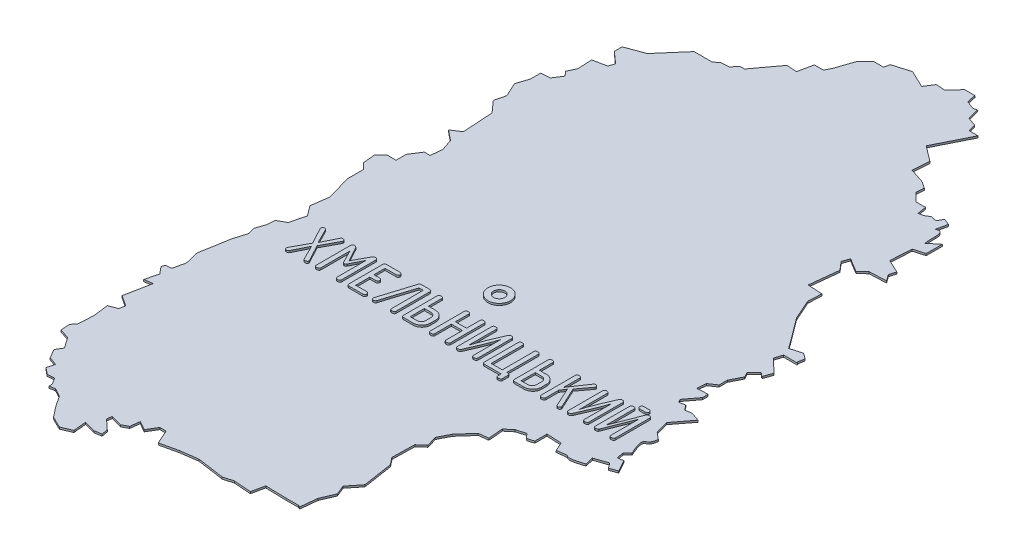
SolidWorks part; units mm, degrees
ref_plane "Спереди" through (0, 0, 0) normal (0, 0, 1) x (1, 0, 0)
ref_plane "Сверху" through (0, 0, 0) normal (0, 1, 0) x (1, 0, 0)
ref_plane "Справа" through (0, 0, 0) normal (1, 0, 0) x (0, 0, -1)
sketch "Эскиз1" plane through (0, 0, 0) normal (0, 1, 0) x (1, 0, 0)
  line B0 (-2553.4518, 8644.0645) -> (-2569.022, 8642.1265)
  line B1 (-2569.022, 8642.1265) -> (-2572.2555, 8660.9301)
  line B2 (-2572.2555, 8660.9301) -> (-2560.5867, 8673.2542)
  line B3 (-2556.6903, 8739.4542) -> (-2575.4889, 8755.0244)
  line B4 (-2575.4889, 8755.0244) -> (-2584.5897, 8789.4185)
  line B5 (-2584.5897, 8789.4185) -> (-2548.2499, 8836.7819)
  line B6 (-2548.2499, 8836.7819) -> (-2572.2555, 8845.2249)
  line B7 (-2572.2555, 8845.2249) -> (-2589.1363, 8841.9889)
  line B8 (-2589.1363, 8841.9889) -> (-2599.5147, 8855.6262)
  line B9 (-2599.5147, 8855.6262) -> (-2615.0773, 8852.3648)
  line B10 (-2615.0773, 8852.3648) -> (-2620.2843, 8860.8103)
  line B11 (-2620.2843, 8860.8103) -> (-2594.3306, 8895.1765)
  line B12 (-2594.3306, 8895.1765) -> (-2594.3306, 8910.132)
  line B13 (-2594.3306, 8910.132) -> (-2623.5203, 8908.8316)
  line B14 (-2623.5203, 8908.8316) -> (-2621.5823, 8932.8498)
  line B15 (-2621.5823, 8932.8498) -> (-2601.4655, 8946.4693)
  line B16 (-2601.4655, 8946.4693) -> (-2601.4655, 8968.5216)
  line B17 (-2601.4655, 8968.5216) -> (-2585.8953, 8999.0168)
  line B18 (-2585.8953, 8999.0168) -> (-2593.0352, 9012.6541)
  line B19 (-2593.0352, 9012.6541) -> (-2574.2214, 9031.4755)
  line B20 (-2574.2214, 9031.4755) -> (-2563.8176, 9023.0274)
  line B21 (-2563.8176, 9023.0274) -> (-2555.3848, 9047.0355)
  line B22 (-2555.3848, 9047.0355) -> (-2591.0692, 9080.787)
  line B23 (-2591.0692, 9080.787) -> (-2584.5897, 9101.5591)
  line B24 (-2584.5897, 9101.5591) -> (-2546.9444, 9101.5591)
  line B25 (-2546.9444, 9101.5591) -> (-2550.2133, 9103.5099)
  line B26 (-2550.2133, 9103.5099) -> (-2546.9444, 9121.6683)
  line B27 (-2546.9444, 9121.6683) -> (-2563.1851, 9133.3574)
  line B28 (-2563.1851, 9133.3574) -> (-2563.8176, 9132.0645)
  line B29 (-2563.8176, 9132.0645) -> (-2593.0352, 9123.6292)
  line B30 (-2593.0352, 9123.6292) -> (-2607.9577, 9144.3835)
  line B31 (-2607.9577, 9144.3835) -> (-2652.7176, 9204.0939)
  line B32 (-2652.7176, 9204.0939) -> (-2676.7384, 9258.5921)
  line B33 (-2676.7384, 9258.5921) -> (-2674.7826, 9294.2816)
  line B34 (-2674.7826, 9294.2816) -> (-2713.7258, 9296.2374)
  line B35 (-2713.7258, 9296.2374) -> (-2705.2905, 9372.8032)
  line B36 (-2705.2905, 9372.8032) -> (-2724.1144, 9394.8809)
  line B37 (-2724.1144, 9394.8809) -> (-2717.6298, 9413.6921)
  line B38 (-2717.6298, 9413.6921) -> (-2681.2799, 9391.6271)
  line B39 (-2681.2799, 9391.6271) -> (-2663.1138, 9408.5029)
  line B40 (-2663.1138, 9408.5029) -> (-2618.3412, 9410.4435)
  line B41 (-2618.3412, 9410.4435) -> (-2630.678, 9427.3243)
  line B42 (-2630.678, 9427.3243) -> (-2625.4888, 9444.8427)
  line B43 (-2625.4888, 9444.8427) -> (-2661.1707, 9461.7057)
  line B44 (-2661.1707, 9461.7057) -> (-2657.9195, 9518.1801)
  line B45 (-2657.9195, 9518.1801) -> (-2628.7273, 9526.6154)
  line B46 (-2628.7273, 9526.6154) -> (-2628.7273, 9569.4449)
  line B47 (-2628.7273, 9569.4449) -> (-2654.0308, 9548.6804)
  line B48 (-2672.8522, 9594.7535) -> (-2666.3548, 9623.9482)
  line B49 (-2666.3548, 9623.9482) -> (-2683.223, 9630.443)
  line B50 (-2683.223, 9630.443) -> (-2691.6659, 9615.518)
  line B51 (-2691.6659, 9615.518) -> (-2707.2234, 9618.759)
  line B52 (-2707.2234, 9618.759) -> (-2718.9379, 9611.6115)
  line B53 (-2718.9379, 9611.6115) -> (-2732.5625, 9608.3653)
  line B54 (-2732.5625, 9608.3653) -> (-2736.4411, 9632.3861)
  line B55 (-2736.4411, 9632.3861) -> (-2761.7445, 9632.3861)
  line B56 (-2761.7445, 9632.3861) -> (-2783.8146, 9654.4587)
  line B57 (-2783.8146, 9654.4587) -> (-2782.5141, 9675.2105)
  line B58 (-2782.5141, 9675.2105) -> (-2799.3772, 9686.8971)
  line B59 (-2799.3772, 9686.8971) -> (-2840.2763, 9700.5242)
  line B60 (-2840.2763, 9700.5242) -> (-2837.0301, 9744.6541)
  line B61 (-2837.0301, 9744.6541) -> (-2877.9089, 9775.7894)
  line B62 (-2877.9089, 9775.7894) -> (-2831.8308, 9867.9533)
  line B63 (-2831.8308, 9867.9533) -> (-2855.8388, 9867.9533)
  line B64 (-2855.8388, 9867.9533) -> (-2861.0509, 9888.0701)
  line B65 (-2861.0509, 9888.0701) -> (-2884.3935, 9896.5055)
  line B66 (-2884.3935, 9896.5055) -> (-2892.8365, 9927.0007)
  line B67 (-2892.8365, 9927.0007) -> (-2901.9246, 9924.4175)
  line B68 (-2901.9246, 9924.4175) -> (-2923.9845, 9932.8554)
  line B69 (-2923.9845, 9932.8554) -> (-2929.1864, 9956.8559)
  line B70 (-2929.1864, 9956.8559) -> (-2956.4228, 9956.8559)
  line B71 (-2956.4228, 9956.8559) -> (-2981.7339, 9928.9438)
  line B72 (-2981.7339, 9928.9438) -> (-3005.742, 9930.8971)
  line B73 (-3005.742, 9930.8971) -> (-3021.3173, 9906.8839)
  line B74 (-3021.3173, 9906.8839) -> (-3067.4158, 9928.9438)
  line B75 (-3067.4158, 9928.9438) -> (-3113.4583, 9915.3243)
  line B76 (-3113.4583, 9915.3243) -> (-3116.707, 9900.4095)
  line B77 (-3116.707, 9900.4095) -> (-3142.6683, 9900.4095)
  line B78 (-3142.6683, 9900.4095) -> (-3166.0287, 9876.3887)
  line B79 (-3166.0287, 9876.3887) -> (-3181.6167, 9830.3182)
  line B80 (-3181.6167, 9830.3182) -> (-3190.0546, 9813.45)
  line B81 (-3190.0546, 9813.45) -> (-3214.0601, 9813.45)
  line B82 (-3214.0601, 9813.45) -> (-3222.5056, 9773.8413)
  line B83 (-3222.5056, 9773.8413) -> (-3249.7395, 9775.7894)
  line B84 (-3249.7395, 9775.7894) -> (-3297.7582, 9710.9128)
  line B85 (-3297.7582, 9710.9128) -> (-3309.4625, 9710.9128)
  line B86 (-3309.4625, 9710.9128) -> (-3323.0744, 9695.3349)
  line B87 (-3323.0744, 9695.3349) -> (-3343.8363, 9694.0497)
  line B88 (-3343.8363, 9694.0497) -> (-3357.4787, 9683.6484)
  line B89 (-3357.4787, 9683.6484) -> (-3405.5101, 9683.6484)
  line B90 (-3405.5101, 9683.6484) -> (-3463.2417, 9616.8134)
  line B91 (-3463.2417, 9616.8134) -> (-3512.5762, 9598.6295)
  line B92 (-3512.5762, 9598.6295) -> (-3512.5762, 9577.8828)
  line B93 (-3512.5762, 9577.8828) -> (-3482.0758, 9550.6286)
  line B94 (-3482.0758, 9550.6286) -> (-3487.2574, 9535.0508)
  line B95 (-3487.2574, 9535.0508) -> (-3512.5762, 9529.8514)
  line B96 (-3512.5762, 9529.8514) -> (-3522.947, 9527.921)
  line B97 (-3522.947, 9527.921) -> (-3521.009, 9488.9777)
  line B98 (-3521.009, 9488.9777) -> (-3531.3976, 9466.928)
  line B99 (-3531.3976, 9466.928) -> (-3521.009, 9454.5836)
  line B100 (-3521.009, 9454.5836) -> (-3536.5868, 9430.5755)
  line B101 (-3536.5868, 9430.5755) -> (-3560.5822, 9429.2623)
  line B102 (-3560.5822, 9429.2623) -> (-3560.5822, 9402.0259)
  line B103 (-3560.5822, 9402.0259) -> (-3570.9682, 9369.5698)
  line B104 (-3570.9682, 9369.5698) -> (-3553.4422, 9331.9448)
  line B105 (-3553.4422, 9331.9448) -> (-3560.5822, 9302.7348)
  line B106 (-3560.5822, 9302.7348) -> (-3533.333, 9272.2344)
  line B107 (-3533.333, 9272.2344) -> (-3528.1311, 9190.4566)
  line B108 (-3528.1311, 9190.4566) -> (-3552.1646, 9174.9016)
  line B109 (-3552.1646, 9174.9016) -> (-3524.9002, 9152.829)
  line B110 (-3524.9002, 9152.829) -> (-3514.5066, 9121.6683)
  line B111 (-3514.5066, 9121.6683) -> (-3517.7527, 9091.168)
  line B112 (-3517.7527, 9091.168) -> (-3533.333, 9091.168)
  line B113 (-3533.333, 9091.168) -> (-3552.1646, 9061.9732)
  line B114 (-3552.1646, 9061.9732) -> (-3552.1646, 9034.7216)
  line B115 (-3552.1646, 9034.7216) -> (-3577.4655, 9034.7216)
  line B116 (-3577.4655, 9034.7216) -> (-3593.0383, 9017.8382)
  line B117 (-3593.0383, 9017.8382) -> (-3589.8125, 8985.3973)
  line B118 (-3589.8125, 8985.3973) -> (-3574.2143, 8969.8246)
  line B119 (-3574.2143, 8969.8246) -> (-3574.2143, 8927.6453)
  line B120 (-3574.2143, 8927.6453) -> (-3555.4056, 8860.8103)
  line B121 (-3555.4056, 8860.8103) -> (-3561.8852, 8814.7246)
  line B122 (-3561.8852, 8814.7246) -> (-3541.7735, 8787.4627)
  line B123 (-3541.7735, 8787.4627) -> (-3552.1646, 8746.6018)
  line B124 (-3552.1646, 8746.6018) -> (-3574.2143, 8734.265)
  line B125 (-3574.2143, 8734.265) -> (-3576.1574, 8712.1949)
  line B126 (-3576.1574, 8712.1949) -> (-3584.6029, 8686.894)
  line B127 (-3584.6029, 8686.894) -> (-3579.4137, 8668.0802)
  line B128 (-3579.4137, 8668.0802) -> (-3589.8125, 8633.6708)
  line B129 (-3589.8125, 8633.6708) -> (-3594.3337, 8606.4268)
  line B130 (-3594.3337, 8606.4268) -> (-3603.4116, 8555.1569)
  line B131 (-3603.4116, 8555.1569) -> (-3594.3337, 8517.5115)
  line B132 (-3594.3337, 8517.5115) -> (-3601.4736, 8485.7133)
  line B133 (-3601.4736, 8485.7133) -> (-3617.0362, 8483.7702)
  line B134 (-3617.0362, 8483.7702) -> (-3620.3052, 8475.3348)
  line B135 (-3620.3052, 8475.3348) -> (-3604.7324, 8456.5033)
  line B136 (-3604.7324, 8456.5033) -> (-3613.1602, 8422.1218)
  line B137 (-3613.1602, 8422.1218) -> (-3591.0901, 8425.3705)
  line B138 (-3591.0901, 8425.3705) -> (-3604.7324, 8355.9421)
  line B139 (-3604.7324, 8355.9421) -> (-3576.1574, 8337.108)
  line B140 (-3576.1574, 8337.108) -> (-3579.4137, 8321.5226)
  line B141 (-3579.4137, 8321.5226) -> (-3601.4736, 8313.105)
  line B142 (-3601.4736, 8313.105) -> (-3596.2844, 8273.5039)
  line B143 (-3596.2844, 8273.5039) -> (-3598.23, 8232.6378)
  line B144 (-3598.23, 8232.6378) -> (-3608.6237, 8219.0006)
  line B145 (-3608.6237, 8219.0006) -> (-3606.6654, 8195.0027)
  line B146 (-3606.6654, 8195.0027) -> (-3580.7167, 8186.5648)
  line B147 (-3580.7167, 8186.5648) -> (-3560.5822, 8158.005)
  line B148 (-3560.5822, 8158.005) -> (-3570.9682, 8140.4841)
  line B149 (-3570.9682, 8140.4841) -> (-3557.3564, 8116.4836)
  line B150 (-3557.3564, 8116.4836) -> (-3534.6462, 8108.0458)
  line B151 (-3534.6462, 8108.0458) -> (-3539.8253, 8087.9315)
  line B152 (-3539.8253, 8087.9315) -> (-3522.947, 8074.3146)
  line B153 (-3522.947, 8074.3146) -> (-3512.5762, 8074.9318)
  line B154 (-3512.5762, 8074.9318) -> (-3504.1357, 8075.5896)
  line B155 (-3504.1357, 8075.5896) -> (-3493.7497, 8058.7012)
  line B156 (-3493.7497, 8058.7012) -> (-3493.102, 8048.9654)
  line B157 (-3493.102, 8048.9654) -> (-3478.8221, 8052.2293)
  line B158 (-3478.8221, 8052.2293) -> (-3456.1145, 8039.895)
  line B159 (-3456.1145, 8039.895) -> (-3437.951, 8012.6332)
  line B160 (-3437.951, 8012.6332) -> (-3415.2434, 7983.4511)
  line B161 (-3415.2434, 7983.4511) -> (-3384.7354, 7968.5134)
  line B162 (-3384.7354, 7968.5134) -> (-3357.4787, 7980.2152)
  line B163 (-3357.4787, 7980.2152) -> (-3360.7248, 8014.5788)
  line B164 (-3360.7248, 8014.5788) -> (-3330.2321, 8006.1486)
  line B165 (-3330.2321, 8006.1486) -> (-3311.3878, 8009.4049)
  line B166 (-3311.3878, 8009.4049) -> (-3314.639, 8026.2755)
  line B167 (-3314.639, 8026.2755) -> (-3340.5978, 8050.2785)
  line B168 (-3340.5978, 8050.2785) -> (-3338.6497, 8063.9082)
  line B169 (-3338.6497, 8063.9082) -> (-3308.1544, 8055.4754)
  line B170 (-3308.1544, 8055.4754) -> (-3292.5842, 8063.9082)
  line B171 (-3292.5842, 8063.9082) -> (-3289.3279, 8089.2142)
  line B172 (-3289.3279, 8089.2142) -> (-3265.3224, 8075.5896)
  line B173 (-3265.3224, 8075.5896) -> (-3249.7395, 8101.5611)
  line B174 (-3249.7395, 8101.5611) -> (-3232.8968, 8101.5611)
  line B175 (-3232.8968, 8101.5611) -> (-3215.9931, 8063.9082)
  line B176 (-3215.9931, 8063.9082) -> (-3169.9327, 8074.3146)
  line B177 (-3169.9327, 8074.3146) -> (-3123.8596, 8080.756)
  line B178 (-3123.8596, 8080.756) -> (-3087.5148, 8075.5896)
  line B179 (-3087.5148, 8075.5896) -> (-3051.8379, 8070.4004)
  line B180 (-3051.8379, 8070.4004) -> (-3026.5243, 8077.5353)
  line B181 (-3026.5243, 8077.5353) -> (-2980.4436, 8074.3146)
  line B182 (-2980.4436, 8074.3146) -> (-2973.2935, 8108.0458)
  line B183 (-2973.2935, 8108.0458) -> (-2916.8573, 8106.7275)
  line B184 (-2916.8573, 8106.7275) -> (-2884.3935, 8106.7275)
  line B185 (-2884.3935, 8106.7275) -> (-2879.217, 8104.1469)
  line B186 (-2879.217, 8104.1469) -> (-2874.6704, 8148.9093)
  line B187 (-2874.6704, 8148.9093) -> (-2859.09, 8185.2643)
  line B188 (-2859.09, 8185.2643) -> (-2869.4736, 8210.5627)
  line B189 (-2869.4736, 8210.5627) -> (-2843.5097, 8243.0087)
  line B190 (-2843.5097, 8243.0087) -> (-2855.8388, 8323.4784)
  line B191 (-2855.8388, 8323.4784) -> (-2870.7817, 8342.31)
  line B192 (-2870.7817, 8342.31) -> (-2869.4736, 8402.0101)
  line B193 (-2869.4736, 8402.0101) -> (-2850.6496, 8418.8732)
  line B194 (-2850.6496, 8418.8732) -> (-2859.09, 8446.1401)
  line B195 (-2859.09, 8446.1401) -> (-2843.5097, 8476.6252)
  line B196 (-2843.5097, 8476.6252) -> (-2811.0713, 8512.9726)
  line B197 (-2811.0713, 8512.9726) -> (-2785.7577, 8516.2263)
  line B198 (-2785.7577, 8516.2263) -> (-2789.0165, 8555.1569)
  line B199 (-2789.0165, 8555.1569) -> (-2770.1799, 8570.7347)
  line B200 (-2770.1799, 8570.7347) -> (-2746.1743, 8577.8569)
  line B201 (-2746.1743, 8577.8569) -> (-2734.4954, 8565.5353)
  line B202 (-2734.4954, 8565.5353) -> (-2717.6298, 8570.7347)
  line B203 (-2717.6298, 8570.7347) -> (-2717.6298, 8603.1807)
  line B204 (-2717.6298, 8603.1807) -> (-2678.0338, 8601.235)
  line B205 (-2678.0338, 8601.235) -> (-2667.6553, 8577.8569)
  line B206 (-2667.6553, 8577.8569) -> (-2640.4062, 8581.103)
  line B207 (-2596.2762, 8586.2973) -> (-2601.4655, 8608.375)
  line B208 (-2601.4655, 8608.375) -> (-2567.0713, 8620.0463)
  line B209 (-2567.0713, 8620.0463) -> (-2556.6903, 8606.4268)
  line B210 (-2556.6903, 8606.4268) -> (-2536.5761, 8613.5489)
  line B211 (-2536.5761, 8613.5489) -> (-2553.4518, 8644.0645)
  spline B212 degree 2 poles (-2560.5867, 8673.2542) (-2579.4005, 8714.1456) (-2569.022, 8717.3968) knots 0.013761 0.013761 0.013761 0.018349 0.018349 0.018349
  spline B213 degree 2 poles (-2569.022, 8717.3968) (-2558.6411, 8720.6252) (-2556.6903, 8739.4542) knots 0.018349 0.018349 0.018349 0.022936 0.022936 0.022936
  spline B214 degree 2 poles (-2654.0308, 9548.6804) (-2655.9739, 9555.165) (-2655.9739, 9579.1731) knots 0.229358 0.229358 0.229358 0.233945 0.233945 0.233945
  spline B215 degree 2 poles (-2655.9739, 9579.1731) (-2655.9739, 9603.2066) (-2672.8522, 9594.7535) knots 0.233945 0.233945 0.233945 0.238532 0.238532 0.238532
  spline B216 degree 2 poles (-2640.4062, 8581.103) (-2633.9165, 8572.6854) (-2596.2762, 8586.2973) knots 0.96789 0.96789 0.96789 0.972477 0.972477 0.972477
sketch_block_instance "Блок22-1"
sketch_block "Блок22"
extrude "Бобышка-Вытянуть1" add sketch "Эскиз1" along normal blind 5 contours B206 B216 B207 B208 B209 B210 B211 B0 B1 B2 B212 B213 B3 B4 B5 B6 B7 B8 B9 B10 B11 B12 B13 B14 B15 B16 B17 B18 B19 B20 B21 B22 B23 B24 B25 B26 B27 B28 B29 B30 B31 B32 B33 B34 B35 B36 B37 B38 B39 B40 B41 region at (-3118.8485, 0, -8946.013)
sketch "Эскиз2" plane through (0, 0, 0) normal (0, 1, 0) x (1, 0, 0)
  line L0 (-3497.8942, 8676.0567) -> (-2178.2616, 8676.0567) construction
  circle A0 centre (-3099.6075, 8857.7067) radius 15
  circle A1 centre (-3099.6075, 8857.7067) radius 30
  text T0 "<b>ХМЕЛЬНИЦЬКИЙ</b>" font "GOST Type AU" height 100
  dimension "D1" = 30
  dimension "D2" = 60
extrude "Бобышка-Вытянуть2" add sketch "Эскиз2" along normal blind 10
scale "Масштаб1" scale about centroid uniform scaling yes scale factor 0.05
